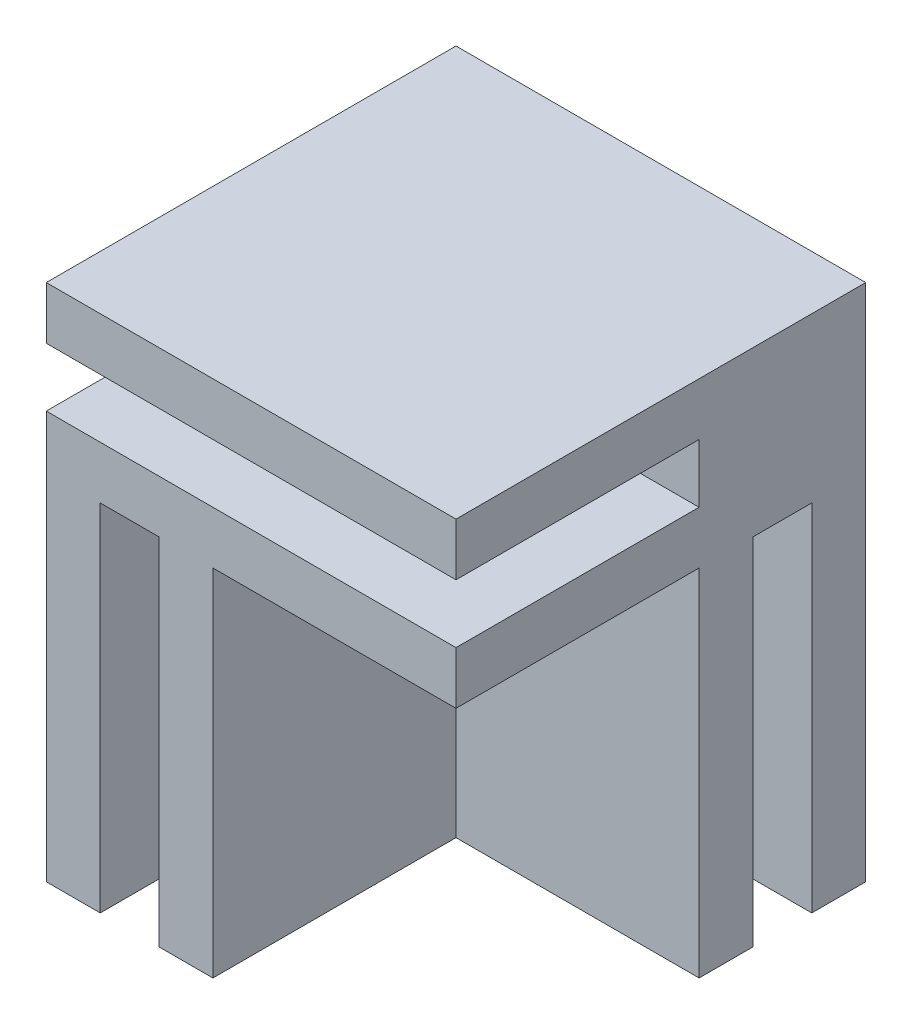
SolidWorks part; units mm, degrees
ref_plane "Plan de face" through (0, 0, 0) normal (0, 0, 1) x (1, 0, 0)
ref_plane "Plan de dessus" through (0, 0, 0) normal (0, 1, 0) x (1, 0, 0)
ref_plane "Plan de droite" through (0, 0, 0) normal (1, 0, 0) x (0, 0, -1)
sketch "Esquisse1" plane through (0, 0, 0) normal (0, 1, 0) x (1, 0, 0)
  line L1 (-35.8867, 13.5315) -> (-5.8867, 13.5315)
  line L2 (-35.8867, 13.5315) -> (-35.8867, -16.4685)
  line L3 (-35.8867, -16.4685) -> (-5.8867, -16.4685)
  line L4 (-5.8867, 13.5315) -> (-5.8867, -16.4685)
  dimension "D1" = 30
  dimension "D2" = 30
extrude "Boss.-Extru.1" add sketch "Esquisse1" along normal blind 38
sketch "Esquisse2" plane through (0, 0, 0) normal (0, -1, 0) x (1, 0, 0)
  line L0 (-5.8867, 16.4685) -> (-5.8867, -13.5315) construction
  line L1 (-5.8867, -9.5815) -> (-23.6867, -9.5815)
  line L2 (-5.8867, -9.5815) -> (-5.8867, -5.2815)
  line L3 (-5.8867, -5.2815) -> (-23.6867, -5.2815)
  line L4 (-23.6867, -9.5815) -> (-23.6867, -5.2815)
  line L5 (-35.8867, 16.4685) -> (-5.8867, 16.4685) construction
  line L6 (-27.6367, 16.4685) -> (-31.9367, 16.4685)
  line L7 (-27.6367, 16.4685) -> (-27.6367, -1.3315)
  line L8 (-27.6367, -1.3315) -> (-31.9367, -1.3315)
  line L9 (-31.9367, 16.4685) -> (-31.9367, -1.3315)
  line L15 (-35.8867, -13.5315) -> (-35.8867, 16.4685) construction
  line L16 (-5.8867, -13.5315) -> (-35.8867, -13.5315) construction
  line L18 (-5.8867, 16.4685) -> (-23.6867, 16.4685)
  line L19 (-5.8867, 16.4685) -> (-5.8867, -1.3315)
  line L20 (-5.8867, -1.3315) -> (-23.6867, -1.3315)
  line L21 (-23.6867, 16.4685) -> (-23.6867, -1.3315)
  dimension "D1" = 4.3
  dimension "D2" = 17.8
  dimension "D3" = 3.95
  dimension "D4" = 4.3
  dimension "D5" = 17.8
  dimension "D6" = 3.95
  dimension "D7" = 3.95
  dimension "D8" = 3.95
extrude "Enlèv. mat.-Extru.1" cut sketch "Esquisse2" against normal blind 26
sketch "Esquisse5" plane through (-35.8867, 0, 0) normal (-1, 0, 0) x (0, 0, 1)
  line L0 (16.4685, 38) -> (16.4685, 0) construction
  line L1 (16.4685, 34.15) -> (-1.3315, 34.15)
  line L2 (16.4685, 34.15) -> (16.4685, 29.85)
  line L3 (16.4685, 29.85) -> (-1.3315, 29.85)
  line L4 (-1.3315, 34.15) -> (-1.3315, 29.85)
  line L6 (-13.5315, 38) -> (16.4685, 38) construction
  dimension "D1" = 17.8
  dimension "D2" = 4.3
  dimension "D3" = 3.85
extrude "Enlèv. mat.-Extru.4" cut sketch "Esquisse5" against normal through all
